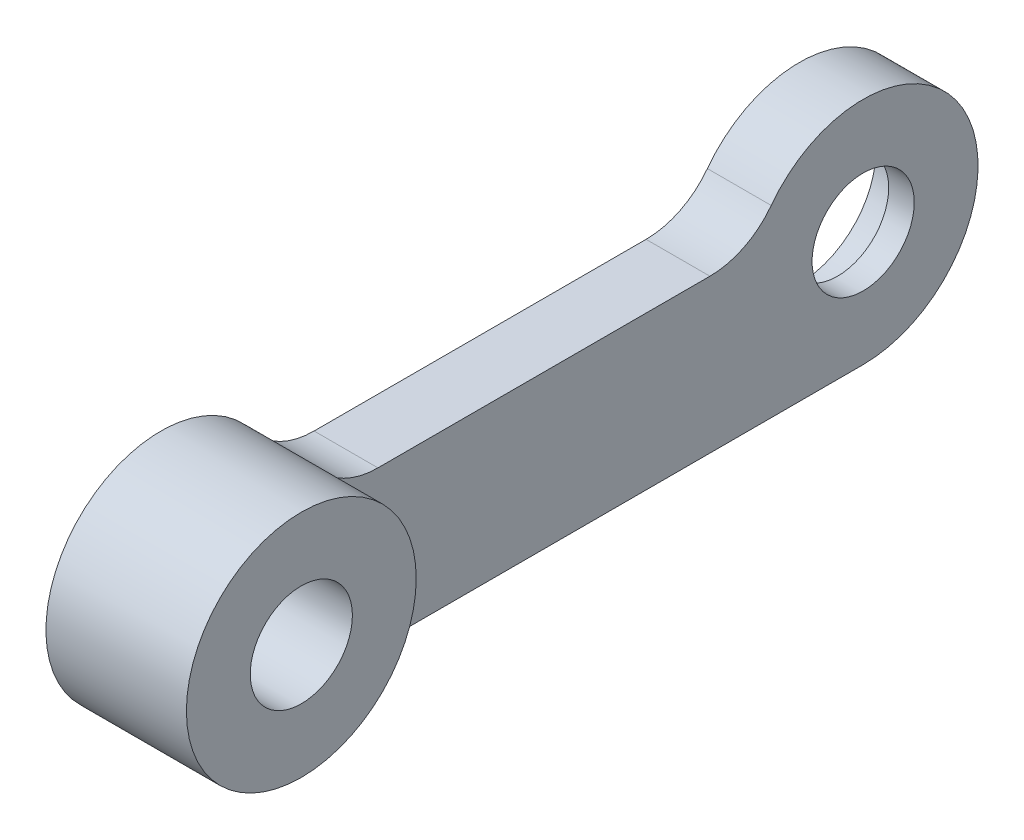
SolidWorks part; units mm, degrees
ref_plane "前视基准面" through (0, 0, 0) normal (0, 0, 1) x (1, 0, 0)
ref_plane "上视基准面" through (0, 0, 0) normal (0, 1, 0) x (1, 0, 0)
ref_plane "右视基准面" through (0, 0, 0) normal (1, 0, 0) x (0, 0, -1)
other "Configuration Table"
sketch "草图1" plane through (0, 0, 0) normal (1, 0, 0) x (0, 0, -1)
  line L1 (0, 0) -> (25, 0)
  line L2 (0, 0) -> (0, -6)
  line L3 (0, -6) -> (25, -6)
  line L4 (25, 0) -> (25, -6)
  circle A0 centre (0, -1.5) radius 4.5
  circle A1 centre (25, -1.5) radius 4.5
  circle A2 centre (0, -1.5) radius 2
  circle A3 centre (25, -1.5) radius 2
  dimension "D1" = 9
  dimension "D2" = 9
  dimension "D4" = 4
  dimension "D3" = 6
  dimension "D5" = 25
extrude "凸台-拉伸1" add sketch "草图1" along normal blind 2.5 contours A0 | L1 L4 L3 L2 | A1
extrude "凸台-拉伸3" add sketch "草图1<5>" against normal blind 3 contours A0
sketch "草图1<5>" plane through (0, 0, 0) normal (1, 0, 0) x (0, 0, -1) same geometry as "草图1"
extrude "切除-拉伸2" cut sketch "草图1<4>" along normal through all both and the other way through all contours L2 A2 | L2 A2 | L4 A3 L1 | L1 A3 L4 region at (0, -1.3854, 0.7577) region at (0, -1.6324, -0.8755) region at (0, -1.3854, -25.7577) region at (0, -1.6324, -24.1245)
sketch "草图1<4>" plane through (0, 0, 0) normal (1, 0, 0) x (0, 0, -1) same geometry as "草图1"
fillet "圆角1" radius 3 2 edges at (1.25, 0, -20.7574) (1.25, 0, -4.2426)
sketch "草图2" plane through (2.5, 0, 0) normal (1, 0, 0) x (0, 0, -1)
  circle A0 centre (0, -1.5) radius 3
  circle A1 centre (25, -1.5) radius 3
  dimension "D1" = 6
extrude "切除-拉伸3" cut sketch "草图2" against normal blind 1.5
ref_plane "基准面1" through (3.5, 0, 0) normal (1, 0, 0) x (0, 0, -1)
mirror "镜向2" about plane through (3.5, 0, 0) normal (1, 0, 0) of bodies 110
sketch "草图3" plane through (3.5, 0, 0) normal (1, 0, 0) x (0, 0, -1)
  line L1 (-8.2827, 6.9332) -> (33.6198, 6.9332)
  line L2 (-8.2827, 6.9332) -> (-8.2827, -10.198)
  line L3 (-8.2827, -10.198) -> (33.6198, -10.198)
  line L4 (33.6198, 6.9332) -> (33.6198, -10.198)
extrude "切除-拉伸4" cut sketch "草图3" against normal through all
